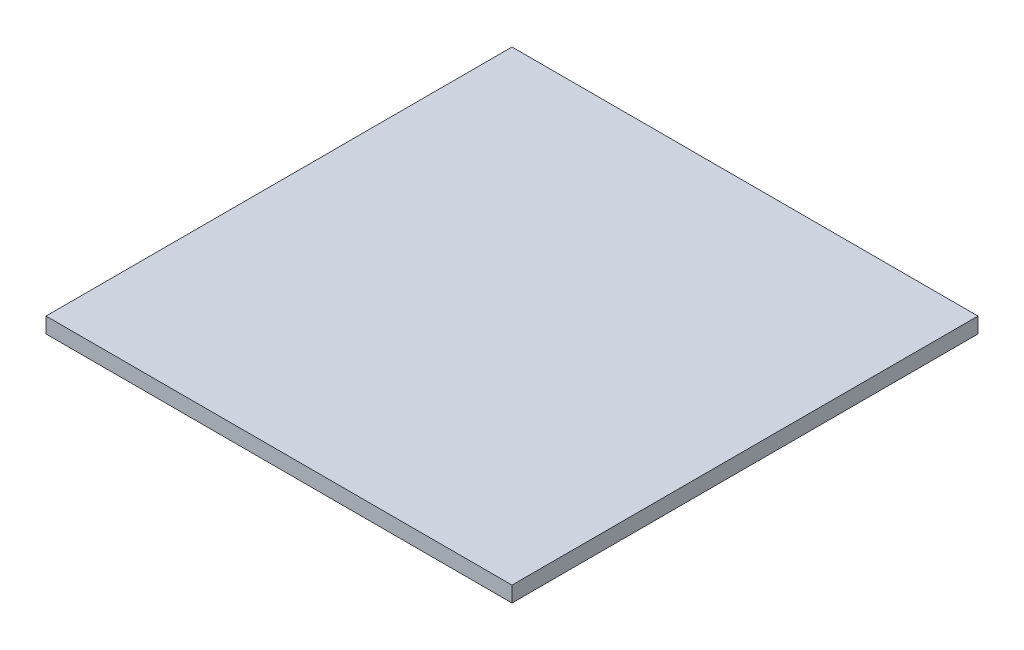
SolidWorks part; units mm, degrees
ref_plane "Front Plane" through (0, 0, 0) normal (0, 0, 1) x (1, 0, 0)
ref_plane "Top Plane" through (0, 0, 0) normal (0, 1, 0) x (1, 0, 0)
ref_plane "Right Plane" through (0, 0, 0) normal (1, 0, 0) x (0, 0, -1)
sketch "Sketch1" plane through (0, 0, 0) normal (0, 1, 0) x (1, 0, 0)
  line L1 (-76.2, -76.2) -> (76.2, -76.2)
  line L2 (-76.2, -76.2) -> (-76.2, 76.2)
  line L3 (-76.2, 76.2) -> (76.2, 76.2)
  line L4 (76.2, -76.2) -> (76.2, 76.2)
  line L5 (-76.2, -76.2) -> (76.2, 76.2) construction
  line L6 (-76.2, 76.2) -> (76.2, -76.2) construction
  point P1 (0, 0)
  dimension "D1" = 152.4
  dimension "D2" = 152.4
extrude "Boss-Extrude1" add sketch "Sketch1" along normal blind 5.08
